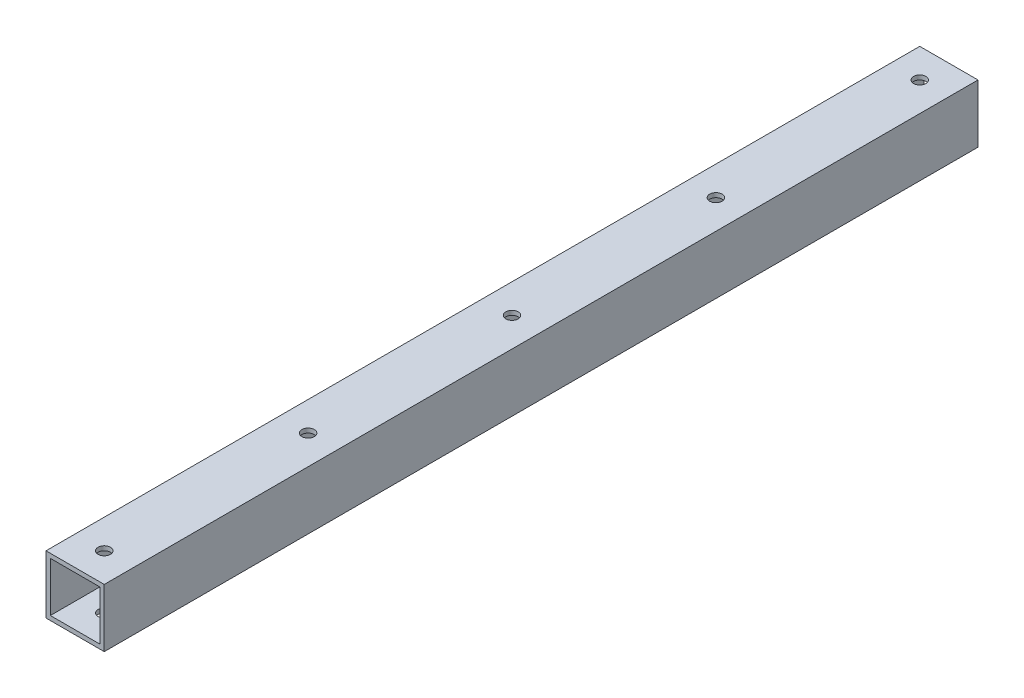
SolidWorks part; units mm, degrees
ref_plane "Front Plane" through (0, 0, 0) normal (0, 0, 1) x (1, 0, 0)
ref_plane "Top Plane" through (0, 0, 0) normal (0, 1, 0) x (1, 0, 0)
ref_plane "Right Plane" through (0, 0, 0) normal (1, 0, 0) x (0, 0, -1)
sketch "Sketch1" plane through (0, 0, 0) normal (0, 0, 1) x (1, 0, 0)
  line L0 (-8.5, -8.5) -> (8.5, -8.5)
  line L1 (-10, -10) -> (10, -10)
  line L2 (-10, -10) -> (-10, 10)
  line L3 (-10, 10) -> (10, 10)
  line L4 (10, -10) -> (10, 10)
  line L5 (-10, -10) -> (10, 10) construction
  line L6 (-10, 10) -> (10, -10) construction
  line L7 (8.5, -8.5) -> (8.5, 8.5)
  line L8 (-8.5, 8.5) -> (8.5, 8.5)
  line L9 (-8.5, -8.5) -> (-8.5, 8.5)
  point P0 (0, 0)
  dimension "D1" = 20
  dimension "D3" = 20
  dimension "D2" = 1.5
extrude "Boss-Extrude1" add sketch "Sketch1" against normal blind 300
sketch "Sketch2" plane through (0, 10, 0) normal (0, 1, 0) x (1, 0, 0)
  line L0 (10, 0) -> (-10, 0) construction
  circle A0 centre (0, 10) radius 2.125
  circle A1 centre (0, 80) radius 2.125
  circle A2 centre (0, 150) radius 2.125
  circle A3 centre (0, 220) radius 2.125
  circle A4 centre (0, 290) radius 2.125
  dimension "D1" = 4.25
  dimension "D2" = 10
  dimension "D4" = 70
  dimension "D3" = 5
extrude "Cut-Extrude1" cut sketch "Sketch2" against normal through all
